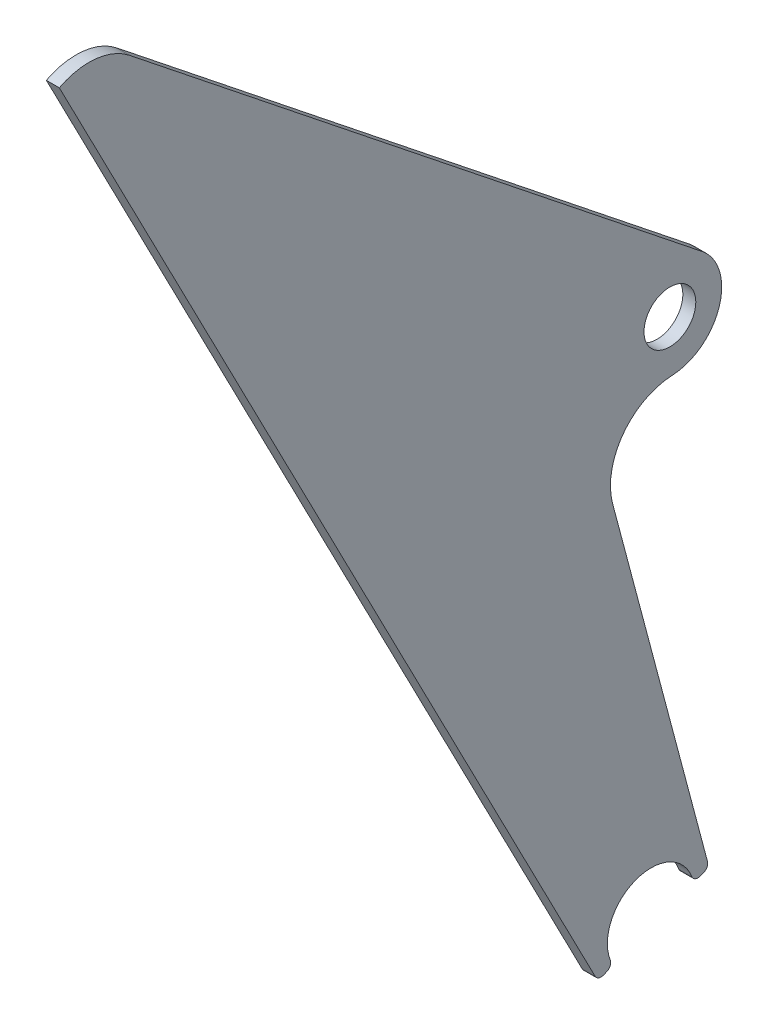
SolidWorks part; units mm, degrees
material "AISI 1020"
ref_plane "Спереди" through (0, 0, 0) normal (0, 0, 1) x (1, 0, 0)
ref_plane "Сверху" through (0, 0, 0) normal (0, 1, 0) x (1, 0, 0)
ref_plane "Справа" through (0, 0, 0) normal (1, 0, 0) x (0, 0, -1)
sketch "Эскиз1" plane through (0, 0, 0) normal (1, 0, 0) x (0, 0, -1)
  line L0 (-161.0976, 311.348) -> (15.777, 170.4424) construction
  line L1 (-11.8838, 116.8323) -> (17.4199, 6.4818) construction
  line L2 (16.2067, 4.1025) -> (15.183, 3.7076) construction
  line L3 (-13.7396, -7.4495) -> (-14.7633, -7.8444) construction
  line L4 (-182.7377, 313.4746) -> (-17.2601, -6.8962) construction
  line L5 (-161.0976, 311.348) -> (15.777, 170.4424)
  line L6 (-11.8838, 116.8323) -> (17.4199, 6.4818)
  line L7 (16.2067, 4.1025) -> (15.183, 3.7076)
  line L8 (-13.7396, -7.4495) -> (-14.7633, -7.8444)
  line L9 (-182.7377, 313.4746) -> (-17.2601, -6.8962)
  arc A0 (-161.0976, 311.348) -> (-182.7377, 313.4746) centre (-173.5594, 295.705) ccw construction
  arc A1 (6.5359, 141.9446) -> (15.777, 170.4424) centre (5.8076, 157.9281) ccw construction
  arc A2 (6.5359, 141.9446) -> (-11.8838, 116.8323) centre (7.4463, 121.9654) ccw construction
  arc A3 (16.2067, 4.1025) -> (17.4199, 6.4818) centre (15.4869, 5.9685) ccw construction
  arc A4 (12.597, 4.8544) -> (15.183, 3.7076) centre (14.4632, 5.5736) ccw construction
  arc A5 (12.597, 4.8544) -> (-12.5937, -4.863) centre (0, 0) ccw construction
  arc A6 (-13.7396, -7.4495) -> (-12.5937, -4.863) centre (-14.4594, -5.5835) ccw construction
  arc A7 (-17.2601, -6.8962) -> (-14.7633, -7.8444) centre (-15.4831, -5.9784) ccw construction
  arc A8 (-161.0976, 311.348) -> (-182.7377, 313.4746) centre (-173.5594, 295.705) ccw
  arc A9 (6.5359, 141.9446) -> (15.777, 170.4424) centre (5.8076, 157.9281) ccw
  arc A10 (6.5359, 141.9446) -> (-11.8838, 116.8323) centre (7.4463, 121.9654) ccw
  arc A11 (16.2067, 4.1025) -> (17.4199, 6.4818) centre (15.4869, 5.9685) ccw
  arc A12 (12.597, 4.8544) -> (15.183, 3.7076) centre (14.4632, 5.5736) ccw
  arc A13 (12.597, 4.8544) -> (-12.5937, -4.863) centre (0, 0) ccw
  arc A14 (-13.7396, -7.4495) -> (-12.5937, -4.863) centre (-14.4594, -5.5835) ccw
  arc A15 (-17.2601, -6.8962) -> (-14.7633, -7.8444) centre (-15.4831, -5.9784) ccw
  circle A16 centre (5.8076, 157.9281) radius 8 construction
  circle A17 centre (5.8076, 157.9281) radius 8
base flange "Базовая кромка1" sketch "Эскиз1" thickness 4 reverse thickness direction yes parameters "D1"=0.74
sketch "Сгиб-Линии1" [suppressed] plane through (0, 0, 0) normal (0, 1, 0) x (1, 0, 0)
sketch "Граничная рамка1" [suppressed] plane through (0, 0, 0) normal (0, 1, 0) x (1, 0, 0)
sheet metal parameters "Листовой металл3" thickness 4 parameters "D1"=0.74
flat pattern "Развертка3" [suppressed]
sketch "Сгиб-Линии2" plane through (0, 0, 0) normal (0, 1, 0) x (1, 0, 0)
sketch3d "Граничная рамка2" [suppressed]
  line L0 (-90.4519, 69.2305, 0) -> (-258.4986, -256.114, 0) construction
  line L1 (9.1783, 17.7696, 0) -> (-158.8684, -307.575, 0) construction
  line L2 (-90.4519, 69.2305, 0) -> (9.1783, 17.7696, 0) construction
  line L3 (-258.4986, -256.114, 0) -> (-158.8684, -307.575, 0) construction
